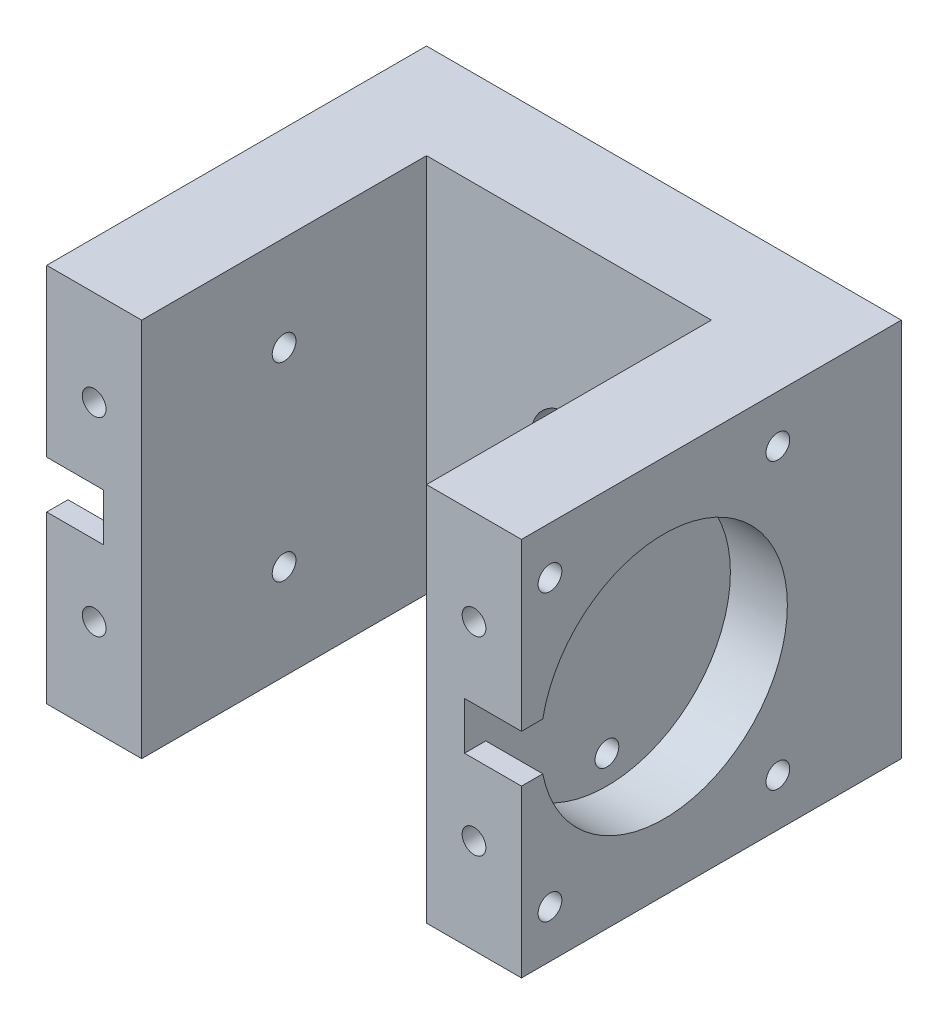
SolidWorks part; units mm, degrees
ref_plane "Front" through (0, 0, 0) normal (0, 0, 1) x (1, 0, 0)
ref_plane "Top" through (0, 0, 0) normal (0, 1, 0) x (1, 0, 0)
ref_plane "Right" through (0, 0, 0) normal (1, 0, 0) x (0, 0, -1)
sketch "Sketch1" plane through (0, 0, 0) normal (0, 1, 0) x (1, 0, 0)
  line L1 (25, -20) -> (-25, -20)
  line L2 (25, -20) -> (25, 20)
  line L3 (25, 20) -> (-25, 20)
  line L4 (-25, -20) -> (-25, 20)
  line L5 (25, -20) -> (-25, 20) construction
  line L6 (25, 20) -> (-25, -20) construction
  point P0 (0, 0)
  dimension "D1" = 50
  dimension "D2" = 40
extrude "Boss-Extrude1" add sketch "Sketch1" along normal blind 40
sketch "Sketch2" plane through (0, 40, 0) normal (0, 1, 0) x (1, 0, 0)
  line L0 (-25, -20) -> (25, -20) construction
  line L1 (-15, -20) -> (15, -20)
  line L2 (-15, -20) -> (-15, 10)
  line L3 (-15, 10) -> (15, 10)
  line L4 (15, -20) -> (15, 10)
  line L5 (-25, 20) -> (-25, -20) construction
  dimension "D1" = 30
  dimension "D2" = 30
  dimension "D3" = 10
extrude "Cut-Extrude1" cut sketch "Sketch2" against normal up to next
sketch "Sketch3" plane through (-25, 0, 0) normal (-1, 0, 0) x (0, 0, 1)
  line L1 (-20, 40) -> (-20, 0) construction
  line L2 (-20, 0) -> (20, 0) construction
  circle A0 centre (5, 20) radius 13
  dimension "D1" = 26
  dimension "D2" = 25
  dimension "D3" = 20
extrude "Cut-Extrude2" cut sketch "Sketch3" against normal blind 6
sketch "Sketch4" plane through (25, 0, 0) normal (1, 0, 0) x (0, 0, -1)
  line L0 (-20, 40) -> (20, 40) construction
  line L1 (20, 40) -> (20, 0) construction
  circle A0 centre (-5, 20) radius 13
  dimension "D1" = 26
  dimension "D2" = 20
  dimension "D3" = 25
extrude "Cut-Extrude3" cut sketch "Sketch4" against normal blind 6
hole_wizard "M3x0.5 Tapped Hole1" positions "Sketch8" profile "Sketch7" tap size "M3x0.5" standard "Ansi Metric"
sketch "Sketch8" plane through (-19, 0, 0) normal (-1, 0, 0) x (0, 0, 1)
  line L1 (20, 40) -> (20, 0) construction
  line L2 (-20, 40) -> (20, 40) construction
  line L3 (-20, 0) -> (20, 0) construction
  point P0 (5, 30)
  point P1 (5, 10)
  dimension "D1" = 15
  dimension "D2" = 10
  dimension "D3" = 15
  dimension "D4" = 10
sketch "Sketch7" plane through (-19, 30, 5) normal (0, 1, 0) x (0, 0, 1)
  line L0 (0, 0) -> (0, 7.2511)
  line L1 (0, 7.2511) -> (1.25, 6.5)
  line L2 (1.25, 6.5) -> (1.25, 0)
  line L5 (1.25, 0) -> (0, 0)
  line L10 (0, 7.2511) -> (-1.25, 6.5) construction
  line L11 (0, -6.35) -> (0, 107.95) construction
  dimension "Tap Drill Dia." = 2.5
  dimension "Tap Drill Depth" = 6.5
  dimension "Drill Angle" = 118
cosmetic thread "Hole Thread1" parameters "D1"=4, "D2"=3
cosmetic thread "Hole Thread2" parameters "D1"=4, "D2"=3
hole_wizard "M3x0.5 Tapped Hole2" positions "Sketch10" profile "Sketch9" tap size "M3x0.5" standard "Ansi Metric"
sketch "Sketch10" plane through (19, 0, 0) normal (1, 0, 0) x (0, 0, -1)
  line L1 (-20, 40) -> (-20, 0) construction
  line L2 (-20, 0) -> (20, 0) construction
  line L3 (-20, 40) -> (20, 40) construction
  point P0 (-5, 30)
  point P1 (-5, 10)
  dimension "D1" = 15
  dimension "D2" = 10
  dimension "D3" = 15
  dimension "D4" = 10
sketch "Sketch9" plane through (19, 30, 5) normal (0, 1, 0) x (0, 0, -1)
  line L0 (0, 0) -> (0, 7.2511)
  line L1 (0, 7.2511) -> (1.25, 6.5)
  line L2 (1.25, 6.5) -> (1.25, 0)
  line L5 (1.25, 0) -> (0, 0)
  line L10 (0, 7.2511) -> (-1.25, 6.5) construction
  line L11 (0, -6.35) -> (0, 107.95) construction
  dimension "Tap Drill Dia." = 2.5
  dimension "Tap Drill Depth" = 6.5
  dimension "Drill Angle" = 118
cosmetic thread "Hole Thread3" parameters "D1"=4, "D2"=3
cosmetic thread "Hole Thread4" parameters "D1"=4, "D2"=3
hole_wizard "M3x0.5 Tapped Hole3" positions "Sketch12" profile "Sketch11" tap size "M3x0.5" standard "Ansi Metric"
sketch "Sketch12" plane through (0, 0, 20) normal (0, 0, 1) x (1, 0, 0)
  line L0 (-25, 40) -> (-25, 0) construction
  line L1 (-25, 40) -> (-15, 40) construction
  line L2 (-25, 0) -> (-15, 0) construction
  line L3 (15, 40) -> (25, 40) construction
  line L4 (25, 40) -> (25, 0) construction
  line L5 (15, 0) -> (25, 0) construction
  point P0 (-20, 30)
  point P1 (-20, 10)
  point P3 (20, 10)
  point P5 (20, 30)
  dimension "D1" = 5
  dimension "D2" = 10
  dimension "D3" = 5
  dimension "D4" = 10
  dimension "D5" = 10
  dimension "D6" = 5
  dimension "D7" = 5
  dimension "D8" = 10
sketch "Sketch11" plane through (-20, 30, 20) normal (1, 0, 0) x (0, -1, 0)
  line L0 (0, 0) -> (0, 4.7511)
  line L1 (0, 4.7511) -> (1.25, 4)
  line L2 (1.25, 4) -> (1.25, 0)
  line L5 (1.25, 0) -> (0, 0)
  line L10 (0, 4.7511) -> (-1.25, 4) construction
  line L11 (0, -6.35) -> (0, 107.95) construction
  dimension "Tap Drill Dia." = 2.5
  dimension "Tap Drill Depth" = 4
  dimension "Drill Angle" = 118
cosmetic thread "Hole Thread5" parameters "D1"=4, "D2"=3
cosmetic thread "Hole Thread6" parameters "D1"=4, "D2"=3
cosmetic thread "Hole Thread7" parameters "D1"=4, "D2"=3
cosmetic thread "Hole Thread8" parameters "D1"=4, "D2"=3
sketch "Sketch13" plane through (0, 0, -10) normal (0, 0, 1) x (1, 0, 0)
  line L0 (15, 40) -> (-15, 40) construction
  line L1 (15, 0) -> (15, 40) construction
  circle A0 centre (0, 20) radius 4
  point P4 (15, 20)
  dimension "D3" = 8
  dimension "D1" = 20
  dimension "D2" = 15
extrude "Cut-Extrude4" cut sketch "Sketch13" against normal blind 8
sketch "Sketch15" plane through (25, 0, 0) normal (1, 0, 0) x (0, 0, -1)
  line L0 (-20, 40) -> (-20, 0) construction
  line L1 (-20, 22.5) -> (-16, 22.5)
  line L2 (-20, 22.5) -> (-20, 17.5)
  line L3 (-20, 17.5) -> (-16, 17.5)
  line L4 (-16, 22.5) -> (-16, 17.5)
  line L5 (-20, 40) -> (20, 40) construction
  dimension "D1" = 5
  dimension "D2" = 4
  dimension "D3" = 17.5
extrude "Cut-Extrude5" cut sketch "Sketch15" against normal blind 6
sketch "Sketch16" plane through (-25, 0, 0) normal (-1, 0, 0) x (0, 0, 1)
  line L1 (20, 22.5) -> (16, 22.5)
  line L2 (20, 22.5) -> (20, 17.5)
  line L3 (20, 17.5) -> (16, 17.5)
  line L4 (16, 22.5) -> (16, 17.5)
  dimension "D1" = 5
  dimension "D2" = 4
extrude "Cut-Extrude6" cut sketch "Sketch16" against normal blind 6
sketch "Sketch17" plane through (25, 0, 0) normal (1, 0, 0) x (0, 0, -1)
  circle A0 centre (-5, 20) radius 10 construction
  dimension "D1" = 20
sketch "Sketch18" plane through (-25, 0, 0) normal (-1, 0, 0) x (0, 0, 1)
  circle A0 centre (5, 20) radius 10 construction
  dimension "D1" = 20
hole_wizard "M3x0.5 Tapped Hole4" positions "Sketch20" profile "Sketch19" tap size "M3x0.5" standard "Ansi Metric"
sketch "Sketch20" plane through (-25, 0, 0) normal (-1, 0, 0) x (0, 0, 1)
  point P0 (-7, 35)
  point P1 (-7, 5)
  point P3 (17, 5)
  point P5 (17, 35)
  dimension "D1" = 12
  dimension "D2" = 15
  dimension "D3" = 15
  dimension "D4" = 12
  dimension "D5" = 12
  dimension "D6" = 15
  dimension "D7" = 15
  dimension "D8" = 12
sketch "Sketch19" plane through (-25, 35, -7) normal (0, 1, 0) x (0, 0, 1)
  line L0 (0, 0) -> (0, 7.2511)
  line L1 (0, 7.2511) -> (1.25, 6.5)
  line L2 (1.25, 6.5) -> (1.25, 0)
  line L5 (1.25, 0) -> (0, 0)
  line L10 (0, 7.2511) -> (-1.25, 6.5) construction
  line L11 (0, -6.35) -> (0, 107.95) construction
  dimension "Tap Drill Dia." = 2.5
  dimension "Tap Drill Depth" = 6.5
  dimension "Drill Angle" = 118
cosmetic thread "Hole Thread9" parameters "D1"=4, "D2"=3
cosmetic thread "Hole Thread10" parameters "D1"=4, "D2"=3
cosmetic thread "Hole Thread11" parameters "D1"=4, "D2"=3
cosmetic thread "Hole Thread12" parameters "D1"=4, "D2"=3
hole_wizard "M3x0.5 Tapped Hole5" positions "Sketch22" profile "Sketch21" tap size "M3x0.5" standard "Ansi Metric"
sketch "Sketch22" plane through (25, 0, 0) normal (1, 0, 0) x (0, 0, -1)
  point P0 (-17, 35)
  point P1 (7, 35)
  point P3 (7, 5)
  point P5 (-17, 5)
  dimension "D1" = 12
  dimension "D2" = 15
  dimension "D3" = 15
  dimension "D4" = 12
  dimension "D5" = 12
  dimension "D6" = 15
  dimension "D7" = 12
  dimension "D8" = 15
sketch "Sketch21" plane through (25, 35, 17) normal (0, 1, 0) x (0, 0, -1)
  line L0 (0, 0) -> (0, 7.2511)
  line L1 (0, 7.2511) -> (1.25, 6.5)
  line L2 (1.25, 6.5) -> (1.25, 0)
  line L5 (1.25, 0) -> (0, 0)
  line L10 (0, 7.2511) -> (-1.25, 6.5) construction
  line L11 (0, -6.35) -> (0, 107.95) construction
  dimension "Tap Drill Dia." = 2.5
  dimension "Tap Drill Depth" = 6.5
  dimension "Drill Angle" = 118
cosmetic thread "Hole Thread13" parameters "D1"=4, "D2"=3
cosmetic thread "Hole Thread14" parameters "D1"=4, "D2"=3
cosmetic thread "Hole Thread15" parameters "D1"=4, "D2"=3
cosmetic thread "Hole Thread16" parameters "D1"=4, "D2"=3
